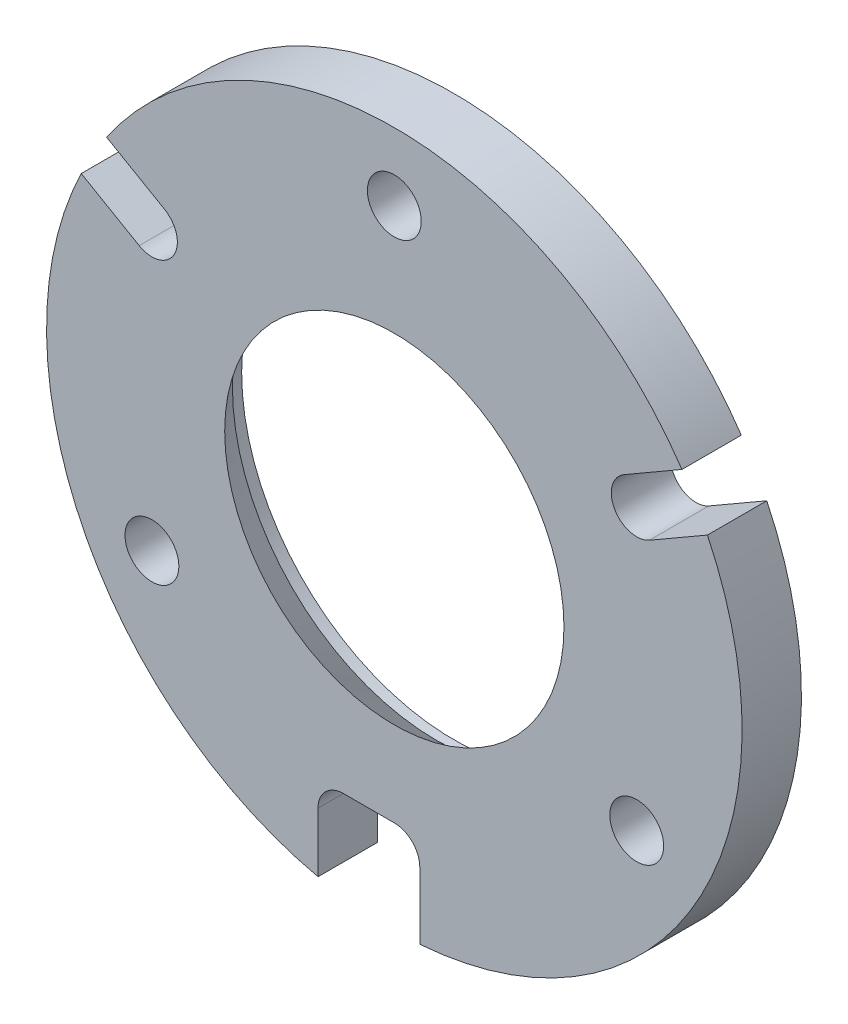
SolidWorks part; units mm, degrees
material "Polyetheretherketone (PEEK)"
ref_plane "Front Plane" through (0, 0, 0) normal (0, 0, 1) x (1, 0, 0)
ref_plane "Top Plane" through (0, 0, 0) normal (0, 1, 0) x (1, 0, 0)
ref_plane "Right Plane" through (0, 0, 0) normal (1, 0, 0) x (0, 0, -1)
sketch "Sketch1" plane through (0, 0, 0) normal (0, 0, 1) x (1, 0, 0)
  circle A0 centre (0, 0) radius 20.5
  circle A1 centre (0, 0) radius 12.5
  circle A2 centre (0, 16.5) radius 1.5875
  circle A3 centre (14.2894, -8.25) radius 1.5875
  circle A4 centre (-14.2894, -8.25) radius 1.5875
  circle A5 centre (0, 0) radius 16.5 construction
  dimension "D1" = 25
  dimension "D2" = 3.175
  dimension "D4" = 41
  dimension "D3" = 33
extrude "Extrude1" add sketch "Sketch1" along normal blind 5
sketch "Sketch2" plane through (0, 0, 5) normal (0, 0, 1) x (1, 0, 0)
  line L0 (1.5, -16.5) -> (1.5, -20.445)
  line L1 (-1.5, -16.5) -> (-1.5, -20.445)
  circle A0 centre (0, 0) radius 16.5 construction
  circle A1 centre (0, 0) radius 20.5
  circle A2 centre (0, 0) radius 20.5
  circle A3 centre (0, -16.5) radius 1.5
  circle M4 centre (0, 0) radius 20.5
  dimension "D2" = 3
  dimension "D1" = 0
extrude "Cut-Extrude1" cut sketch "Sketch2" against normal through all contours A3 L1 L0 M4 | A3 region at (0, -16.5, 5) region at (0, -19.06, 5)
ref_axis "Axis1" through (0, 0, 5) along (0, 0, -1)
pattern_circular "CirPattern1" count 3 over 360 about axis through (0, 0, 5) along (0, 0, -1) of "Cut-Extrude1"
sketch "Sketch3" plane through (0, 0, 0) normal (0, 1, 0) x (1, 0, 0)
  line L0 (0, 0) -> (0, -5)
  line L1 (-12.5, -5) -> (12.5, -5) construction
  line L2 (-20.5, -5) -> (-1.5, -5) construction
  line L3 (-12.5, -5) -> (-10, -5)
  line L4 (-12.5, -5) -> (-12.5, -2.5)
  line L5 (-12.5, -2.5) -> (-10, -2.5)
  line L6 (-10, -5) -> (-10, -2.5)
  dimension "D1" = 10
  dimension "D2" = 2.5
  dimension "D3" = 12.5
revolve "Revolve1" add sketch "Sketch3" angle 360 about L0 region at (-11.25, 0, 3.75)
sketch "Sketch4" plane through (0, 0, 0) normal (0, 1, 0) x (1, 0, 0)
  line L0 (0, 0) -> (0, -1.5)
  line L1 (0, -1.5) -> (-20.5, -1.5)
  line L2 (-20.5, 0) -> (-20.5, -5) construction
  line L3 (-20.5, -1.5) -> (-20.5, 0)
  line L4 (-20.5, 0) -> (0, 0)
  dimension "D1" = 1.5
revolve "Cut-Revolve1" cut sketch "Sketch4" angle 360 about L0
sketch "Sketch5" plane through (0, 0, 5) normal (0, 0, 1) x (1, 0, 0)
  line L0 (0, -16.5) -> (-3, -16.5) construction
  line L1 (0, -15) -> (-3, -15)
  line L2 (-4.5, -16.5) -> (-4.5, -20)
  line L9 (13.5394, 9.549) -> (16.9559, 11.5216)
  line L10 (-16.9559, 11.5216) -> (-13.5394, 9.549)
  line L11 (-15.0394, 6.951) -> (-18.4559, 8.9235)
  line L12 (-1.5, -20.445) -> (-1.5, -16.5)
  line L13 (1.5, -16.5) -> (1.5, -20.445)
  line L14 (18.4559, 8.9235) -> (15.0394, 6.951)
  line L15 (13.5394, 9.549) -> (16.9559, 11.5216)
  line L16 (-16.9559, 11.5216) -> (-13.5394, 9.549)
  line L17 (-15.0394, 6.951) -> (-18.4559, 8.9235)
  line L18 (-1.5, -20.445) -> (-1.5, -16.5)
  line L19 (1.5, -16.5) -> (1.5, -20.445)
  line L20 (18.4559, 8.9235) -> (15.0394, 6.951)
  circle A2 centre (-3, -16.5) radius 1.5
  arc A4 (1.5, -16.5) -> (-1.5, -16.5) centre (0, -16.5) ccw construction
  arc A5 (-18.4559, 8.9235) -> (-1.5, -20.445) centre (0, 0) ccw construction
  arc A12 (13.5394, 9.549) -> (15.0394, 6.951) centre (14.2894, 8.25) ccw
  arc A13 (16.9559, 11.5216) -> (-16.9559, 11.5216) centre (0, 0) ccw
  arc A14 (-15.0394, 6.951) -> (-13.5394, 9.549) centre (-14.2894, 8.25) ccw
  arc A15 (-18.4559, 8.9235) -> (-1.5, -20.445) centre (0, 0) ccw
  arc A16 (1.5, -16.5) -> (-1.5, -16.5) centre (0, -16.5) ccw
  arc A17 (1.5, -20.445) -> (18.4559, 8.9235) centre (0, 0) ccw
  arc A18 (13.5394, 9.549) -> (15.0394, 6.951) centre (14.2894, 8.25) ccw
  arc A19 (16.9559, 11.5216) -> (-16.9559, 11.5216) centre (0, 0) ccw
  arc A20 (-15.0394, 6.951) -> (-13.5394, 9.549) centre (-14.2894, 8.25) ccw
  arc A21 (-18.4559, 8.9235) -> (-1.5, -20.445) centre (0, 0) ccw
  arc A22 (1.5, -16.5) -> (-1.5, -16.5) centre (0, -16.5) ccw
  arc A23 (1.5, -20.445) -> (18.4559, 8.9235) centre (0, 0) ccw
  arc M22 (-18.4559, 8.9235) -> (-1.5, -20.445) centre (0, 0) ccw
  line M23 (-1.5, -20.445) -> (-1.5, -16.5)
  arc M24 (-1.5, -16.5) -> (1.5, -16.5) centre (0, -16.5) cw
  dimension "D1" = 3
  dimension "D2" = 3
  dimension "D3" = 0
extrude "Cut-Extrude2" cut sketch "Sketch5" against normal through all contours A2 L1 M24 | A2 | A2 L2 M22 M23 region at (-1.5, -15.3351, 5) region at (-3, -16.5, 5) region at (-2.957, -18.9508, 5)
sketch "Sketch6" plane through (0, 0, 0) normal (0, 1, 0) x (1, 0, 0)
  line L6 (-10, -5) -> (-12.0453, -2.5)
  line L7 (-20.5, -5) -> (-4.5, -5) construction
  line L8 (-10, -5) -> (10, -5) construction
  line L9 (-12.0453, -2.5) -> (-10, -2.5)
  line L10 (-10, -2.5) -> (-10, -5)
  line L11 (0, 0) -> (0, -8.2723) construction
revolve "Cut-Revolve2" cut sketch "Sketch6" angle 360 about L11
